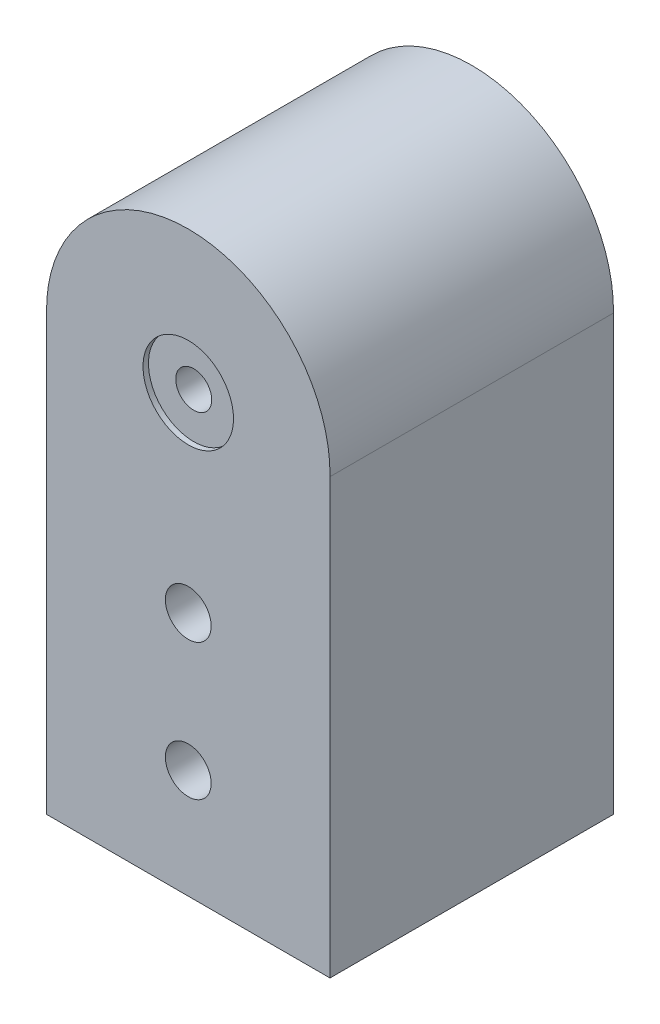
SolidWorks part; units mm, degrees
material "打印件"
ref_plane "前视基准面" through (0, 0, 0) normal (0, 0, 1) x (1, 0, 0)
ref_plane "上视基准面" through (0, 0, 0) normal (0, 1, 0) x (1, 0, 0)
ref_plane "右视基准面" through (0, 0, 0) normal (1, 0, 0) x (0, 0, -1)
sketch "草图2" plane through (0, 0, 0) normal (0, 0, 1) x (1, 0, 0)
  line L0 (0, 0) -> (0, 30)
  line L1 (26, 30) -> (26, 0)
  line L2 (26, 0) -> (0, 0)
  line L3 (13, 0) -> (13, 50) construction
  arc A0 (0, 30) -> (26, 30) centre (13, 40) cw
  dimension "D1" = 40
  dimension "D2" = 26
  dimension "D3" = 30
extrude "凸台-拉伸1" add sketch "草图2" along normal blind 26
sketch "草图3" plane through (0, 0, 0) normal (0, -1, 0) x (1, 0, 0)
  line L0 (0, 26) -> (26, 26) construction
  line L1 (3, 23) -> (23, 23)
  line L2 (3, 23) -> (3, 3)
  line L3 (3, 3) -> (23, 3)
  line L4 (23, 23) -> (23, 3)
  line L5 (0, 26) -> (0, 0) construction
  line L6 (0, 0) -> (26, 0) construction
  line L7 (26, 26) -> (26, 0) construction
  dimension "D1" = 3
  dimension "D2" = 3
  dimension "D3" = 3
  dimension "D4" = 3
extrude "切除-拉伸1" cut sketch "草图3" against normal blind 30
sketch "草图4" plane through (0, 0, 26) normal (0, 0, 1) x (1, 0, 0)
  circle A0 centre (13, 40) radius 4.15
  circle A1 centre (13, 40) radius 1.65
  dimension "D1" = 8.3
  dimension "D2" = 3.3
extrude "切除-拉伸2" cut sketch "草图4" against normal through all contours A1 region at (13, 40, 26)
extrude "切除-拉伸3" cut sketch "草图4<3>" against normal blind 0.5
sketch "草图4<3>" plane through (0, 0, 26) normal (0, 0, 1) x (1, 0, 0) same geometry as "草图4"
extrude "切除-拉伸4" cut sketch "草图4<4>" along normal blind 0.5 from surface starting at face at (14.65, 40, 0)
sketch "草图4<4>" plane through (0, 0, 26) normal (0, 0, 1) x (1, 0, 0) same geometry as "草图4"
sketch "草图5" plane through (0, 0, 26) normal (0, 0, 1) x (1, 0, 0)
  line L0 (13, 0) -> (13, 40) construction
  line L1 (0, 0) -> (26, 0) construction
  circle A0 centre (13, 22.5) radius 2.1
  circle A1 centre (13, 10) radius 2.1
  dimension "D1" = 4.2
  dimension "D2" = 4.2
  dimension "D3" = 10
  dimension "D4" = 12.5
extrude "切除-拉伸5" cut sketch "草图5" against normal through all
sketch "草图6" plane through (0, 0, 26) normal (0, 0, 1) x (1, 0, 0)
  line L0 (0, 30) -> (0, 39.8219)
  line L1 (26, 30) -> (26, 39.8219)
  arc A0 (26, 30) -> (0, 30) centre (13, 40) ccw
  arc A1 (26, 39.8219) -> (0, 39.8219) centre (13, 40) ccw
  arc A2 (26, 30) -> (0, 30) centre (13, 40) ccw construction
  dimension "D1" = 3.4
extrude "切除-拉伸6" cut sketch "草图6" against normal blind 67
